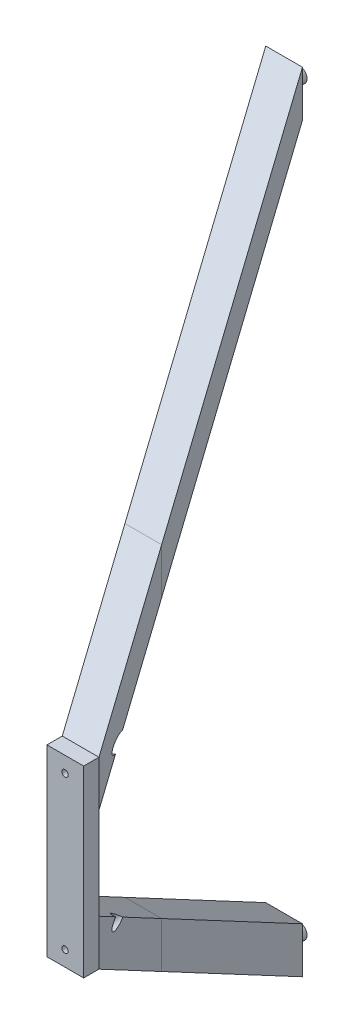
SolidWorks part; units mm, degrees
ref_plane "Front Plane" through (0, 0, 0) normal (1, 0, 0) x (0, 1, 0)
ref_plane "Top Plane" through (0, 0, 0) normal (0, 0, 1) x (0, 1, 0)
ref_plane "Right Plane" through (0, 0, 0) normal (0, 1, 0) x (-1, 0, 0)
sketch "Sketch1" plane through (0, 0, 0) normal (0, 0, -1) x (1, 0, 0)
  line L0 (0, 0) -> (0, 119.9996) construction
  line L1 (0, 0) -> (0, 119.9996)
  line L2 (24, 0) -> (24, 119.9996)
  line L3 (11.7634, 12.289) -> (11.3368, 12.233) construction
  line L4 (11.3368, 112.0708) -> (11.7633, 112.127) construction
  line L5 (0, 119.9996) -> (24, 119.9996)
  line L6 (0, 0) -> (24, 0)
  circle A0 centre (11.8188, 10.197) radius 2.0814
  circle A1 centre (11.8188, 110.0343) radius 2.082
  point P12 (11.5501, 12.261)
  point P19 (11.5501, 112.0989)
  dimension "D1" = 24
extrude "Boss-Extrude1" add sketch "Sketch1" along normal blind 10
sketch "Sketch4" plane through (0, -119.9996, 0) normal (0, -1, 0) x (1, 0, 0)
  line L9 (0, -10) -> (4.8773, 0)
  line L13 (24, 0) -> (0, 0) construction
  line L15 (0, -10) -> (0, 0) construction
  dimension "D1" = 26
ref_plane "Plane1" through (3.9401, 0, -1.9217) normal (-0.8988, 0, 0.4384) x (0.4384, 0, 0.8988)
sketch "Sketch6" plane through (3.9401, 0, -1.9217) normal (-0.8988, 0, 0.4384) x (0.4384, 0, 0.8988)
  line L0 (-8.9879, 0) -> (-297.9407, 197.5002)
  line L1 (-8.9879, -30) -> (-297.9407, 167.5002)
  line L2 (-8.9879, -30) -> (-8.9879, 0)
  line L3 (-297.9407, 197.5002) -> (-297.9407, 167.5002)
  line L6 (-297.9407, -287.4998) -> (-297.9407, -317.4998)
  line L7 (0, -59.9998) -> (-8.9879, -59.9998) construction
  line L9 (-8.9879, -119.9996) -> (-297.9407, -317.4998)
  line L10 (-8.9879, -89.9996) -> (-8.9879, -119.9996)
  line L11 (-8.9879, -89.9996) -> (-297.9407, -287.4998)
  line L13 (-8.9879, -119.9996) -> (-8.9879, 0) construction
  line L14 (-8.9879, 0) -> (0, 0) construction
  line L15 (-8.9879, -119.9996) -> (0, -119.9996) construction
  line L16 (0, -119.9996) -> (0, 0) construction
  point P1 (-297.9407, 182.5002)
  point P2 (-297.9407, -302.4998)
  dimension "D2" = 350
  dimension "D3" = 485
  dimension "D1" = 30
extrude "Boss-Extrude2" add sketch "Sketch6" along direction (-1, 0, 0) on the side against the normal up to vertex (21.5711 mm away) up to point (24, 0, -10)
sketch "Sketch7" plane through (0, 0, -269.709) normal (0, 0, -1) x (1, 0, 0)
  line L0 (-126.6685, -197.5002) -> (-126.6685, -167.5002) construction
  line L1 (-102.6685, -197.5002) -> (-126.6685, -197.5002) construction
  line L2 (-126.6685, 287.4998) -> (-126.6685, 317.4998) construction
  circle A0 centre (-114.6685, -182.5002) radius 5
  circle A1 centre (-114.6685, 302.4998) radius 5
  point P6 (-126.6685, -182.5002)
  point P9 (-114.6685, -197.5002)
  point P13 (-126.6685, 302.4998)
  dimension "D1" = 10
  dimension "D2" = 10
extrude "Boss-Extrude3" add sketch "Sketch7" along normal blind 10
sketch "Sketch8" plane through (0, 0, -10) normal (0, 0, -1) x (1, 0, 0)
  circle A0 centre (11.8188, 110.0343) radius 2.082 construction
  circle A1 centre (11.8188, 110.0343) radius 2.082
  circle A2 centre (11.8188, 10.197) radius 2.0814 construction
  circle A3 centre (11.8188, 10.197) radius 2.0814
extrude "Cut-Extrude1" cut sketch "Sketch8" along normal through all
sketch "Sketch9" plane through (0, 0, -10) normal (0, 0, -1) x (1, 0, 0)
  circle A2 centre (11.8188, 10.197) radius 4.0814
  circle A3 centre (11.8188, 10.197) radius 4.0814
  circle A5 centre (11.8188, 110.0343) radius 4.082
  circle A6 centre (11.8188, 110.0343) radius 4.082
  dimension "D1" = 2
  dimension "D2" = 2
extrude "Cut-Extrude2" cut sketch "Sketch9" along normal through all from offset 10
ref_plane "Plane2" through (0, 0, -90) normal (0, 0, -1) x (-1, 0, 0)
split "Split1" trim tools "Plane2" bodies to split 109 resulting bodies 110 111 112
sketch "Sketch10" plane through (0, 0, -90) normal (0, 0, -1) x (-1, 0, 0)
  line L8 (18.0186, -177.837) -> (36.0186, -177.837)
  line L9 (36.0186, -177.837) -> (36.0186, -153.837)
  line L10 (18.0186, -153.837) -> (18.0186, -177.837)
  line L11 (36.0186, -153.837) -> (18.0186, -153.837)
  line L12 (18.0186, -177.837) -> (36.0186, -177.837)
  line L13 (36.0186, -177.837) -> (36.0186, -153.837)
  line L14 (18.0186, -153.837) -> (18.0186, -177.837)
  line L15 (36.0186, -153.837) -> (18.0186, -153.837)
  dimension "D1" = 3
extrude "Cut-Extrude3" cut sketch "Sketch10" along direction (0.3619, 0.5643, 0.742) on the side of the normal blind 30
sketch "Sketch11" plane through (0, 0, -90) normal (0, 0, -1) x (-1, 0, 0)
  line L8 (36.0186, 57.8374) -> (18.0186, 57.8374)
  line L9 (36.0186, 33.8374) -> (36.0186, 57.8374)
  line L10 (18.0186, 57.8374) -> (18.0186, 33.8374)
  line L11 (18.0186, 33.8374) -> (36.0186, 33.8374)
  line L12 (36.0186, 57.8374) -> (18.0186, 57.8374)
  line L13 (36.0186, 33.8374) -> (36.0186, 57.8374)
  line L14 (18.0186, 57.8374) -> (18.0186, 33.8374)
  line L15 (18.0186, 33.8374) -> (36.0186, 33.8374)
  dimension "D1" = 3
extrude "Cut-Extrude4" cut sketch "Sketch11" along direction (-0.3619, 0.5643, -0.742) on the side of the normal blind 30
sketch "Sketch12" plane through (0, 0, -90) normal (0, 0, -1) x (-1, 0, 0)
  line L8 (35.8186, -177.637) -> (35.8186, -154.037)
  line L9 (18.2186, -177.637) -> (35.8186, -177.637)
  line L10 (18.2186, -154.037) -> (18.2186, -177.637)
  line L11 (35.8186, -154.037) -> (18.2186, -154.037)
  line L12 (35.8186, -177.637) -> (35.8186, -154.037)
  line L13 (18.2186, -177.637) -> (35.8186, -177.637)
  line L14 (18.2186, -154.037) -> (18.2186, -177.637)
  line L15 (35.8186, -154.037) -> (18.2186, -154.037)
  dimension "D1" = 3.2
extrude "Boss-Extrude4" add sketch "Sketch12" along direction (-0.3619, -0.5643, -0.742) on the side of the normal blind 30 separate body
sketch "Sketch13" plane through (0, 0, -90) normal (0, 0, -1) x (-1, 0, 0)
  line L8 (35.8186, 57.6374) -> (18.2186, 57.6374)
  line L9 (35.8186, 34.0374) -> (35.8186, 57.6374)
  line L10 (18.2186, 57.6374) -> (18.2186, 34.0374)
  line L11 (18.2186, 34.0374) -> (35.8186, 34.0374)
  line L12 (35.8186, 57.6374) -> (18.2186, 57.6374)
  line L13 (35.8186, 34.0374) -> (35.8186, 57.6374)
  line L14 (18.2186, 57.6374) -> (18.2186, 34.0374)
  line L15 (18.2186, 34.0374) -> (35.8186, 34.0374)
  dimension "D1" = 3.2
extrude "Boss-Extrude5" add sketch "Sketch13" along direction (-0.3619, 0.5643, -0.742) on the side of the normal blind 30 separate body
combine bodies "Combine1" operation type add bodies to combine 116 115 111
